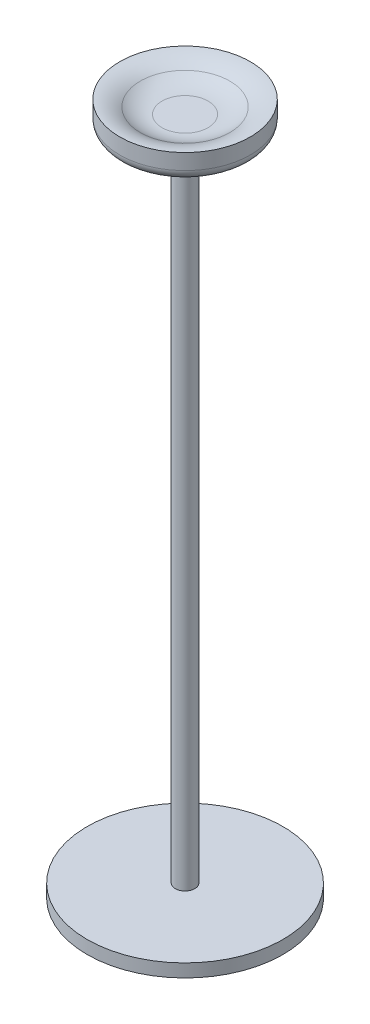
SolidWorks part; units mm, degrees
ref_plane "Front Plane" through (0, 0, 0) normal (0, 0, 1) x (1, 0, 0)
ref_plane "Top Plane" through (0, 0, 0) normal (0, 1, 0) x (1, 0, 0)
ref_plane "Right Plane" through (0, 0, 0) normal (1, 0, 0) x (0, 0, -1)
sketch "Sketch1" plane through (0, 0, 0) normal (0, 1, 0) x (1, 0, 0)
  circle A0 centre (0, 0) radius 75
  dimension "D1" = 150
extrude "Boss-Extrude1" add sketch "Sketch1" along normal blind 10
sketch "Sketch2" plane through (0, 10, 0) normal (0, 1, 0) x (1, 0, 0)
  circle A0 centre (0, 0) radius 7.5
  dimension "D1" = 15
extrude "Boss-Extrude2" add sketch "Sketch2" along normal blind 500
sketch "Sketch3" plane through (0, 510, 0) normal (0, 1, 0) x (1, 0, 0)
  circle A0 centre (0, 0) radius 50
  dimension "D1" = 100
extrude "Boss-Extrude3" add sketch "Sketch3" along normal blind 20 contours A0
fillet "Fillet1" radius 8 2 edges at (0, 510, 7.5) (0, 510, 50)
sketch "Sketch4" plane through (0, 530, 0) normal (0, 1, 0) x (1, 0, 0)
  circle A0 centre (0, 0) radius 40.0092
extrude "Cut-Extrude1" cut sketch "Sketch4" against normal blind 10
fillet "Fillet3" radius 30 1 edges at (0, 520, 40.0092)
fillet "Fillet4" radius 30 1 edges at (0, 530, 40.0092)
